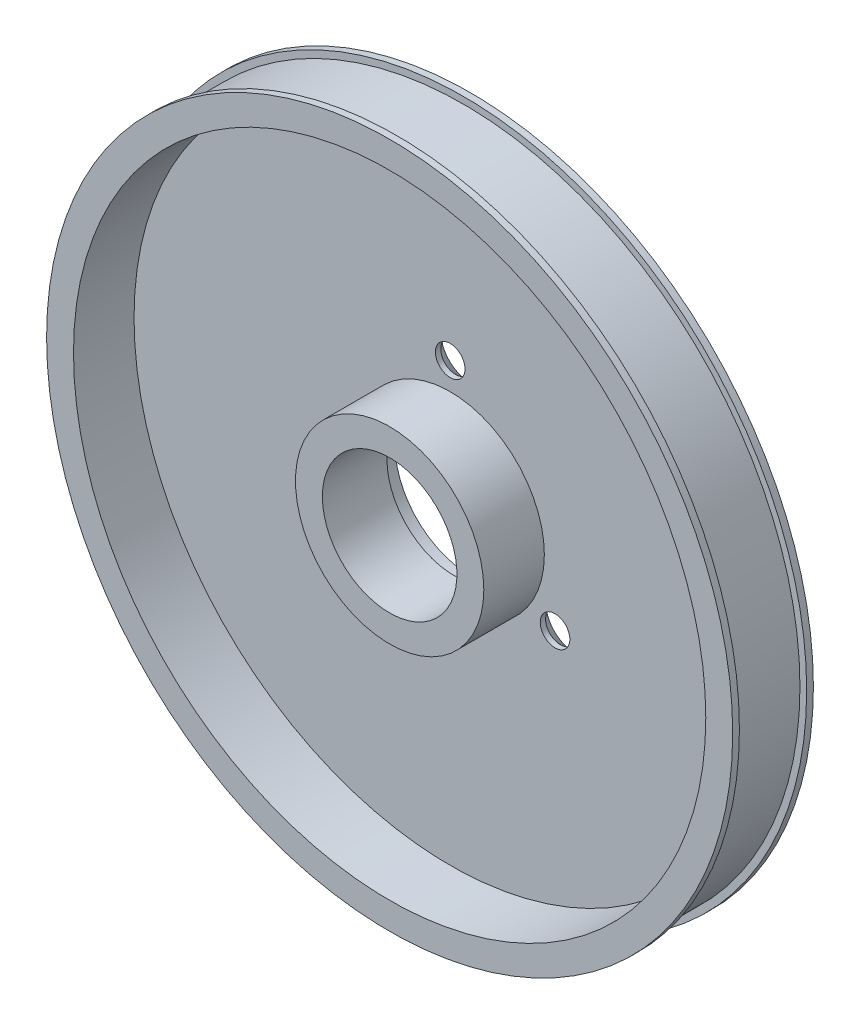
SolidWorks part; units mm, degrees
material "6061 Alloy"
ref_plane "Front Plane" through (0, 0, 0) normal (0, 0, 1) x (1, 0, 0)
ref_plane "Top Plane" through (0, 0, 0) normal (0, 1, 0) x (1, 0, 0)
ref_plane "Right Plane" through (0, 0, 0) normal (1, 0, 0) x (0, 0, -1)
sketch "Sketch1" plane through (0, 0, 0) normal (0, 1, 0) x (1, 0, 0)
  line L0 (25.5, 0) -> (0, 0)
  line L1 (0, 0) -> (0, -6)
  line L2 (0, -6) -> (25.5, -6)
  line L3 (25.5, -6) -> (25.5, -5.5)
  line L4 (25.5, -5.5) -> (25, -5.5)
  line L5 (25, -5.5) -> (25, -0.5)
  line L6 (25, -0.5) -> (25.5, -0.5)
  line L7 (25.5, -0.5) -> (25.5, 0)
  line L8 (0, 0) -> (0, -6) construction
revolve "Revolve1" add sketch "Sketch1" angle 360 about L8 reverse direction yes
hole_wizard "M42 Clearance Hole1" positions "Sketch3" profile "Sketch2" hole size "M42" standard "ANSI Metric"
sketch "Sketch3" plane through (0, 0, 6) normal (0, 0, 1) x (1, 0, 0)
  point P0 (0, 0)
sketch "Sketch2" plane through (0, 0, 6) normal (1, 0, 0) x (0, -1, 0)
  line L0 (0, 0) -> (0, 4.5)
  line L1 (0, 4.5) -> (23.5, 4.5)
  line L2 (23.5, 4.5) -> (23.5, 0)
  line L5 (23.5, 0) -> (0, 0)
  line L10 (0, 4.5) -> (-23.5, 4.5) construction
  line L11 (0, -6.35) -> (0, 107.95) construction
  dimension "Hole Dia." = 47
  dimension "Hole Depth" = 4.5
  dimension "Drill Angle" = 180
sketch "Sketch4" plane through (0, 0, 0) normal (0, 1, 0) x (1, 0, 0)
  line L0 (7, -1.5) -> (0, -1.5)
  line L1 (0, -1.5) -> (0, -6)
  line L2 (0, -6) -> (7, -6)
  line L3 (7, -6) -> (7, -1.5)
  line L4 (0, -1.5) -> (0, -6) construction
revolve "Revolve2" add sketch "Sketch4" angle 360 about L4 reverse direction yes
hole_wizard "CSK for M2 Flat Head Machine Screw1" positions "Sketch6" profile "Sketch5" countersink size "M2" standard "ANSI Metric"
sketch "Sketch6" plane through (0, 0, 0) normal (0, 0, -1) x (-1, 0, 0)
  point P0 (-7.7942, -4.5)
  point P1 (7.7942, -4.5)
  point P2 (0, 9)
sketch "Sketch5" plane through (7.7942, -4.5, 0) normal (1, 0, 0) x (0, 1, 0)
  line L0 (0, 0) -> (0, 6)
  line L1 (0, 6) -> (1.1, 6)
  line L2 (1.1, 6) -> (1.1, 1.1)
  line L3 (1.1, 1.1) -> (2.2, 0)
  line L5 (2.2, 0) -> (0, 0)
  line L6 (-1.1, 1.1) -> (-2.2, 0) construction
  line L11 (0, -6.35) -> (0, 107.95) construction
  dimension "Thru Hole Dia." = 2.2
  dimension "Thru Hole Depth" = 6
  dimension "Near C'Sink Dia." = 4.4
  dimension "Near C'Sink Angle" = 90
hole_wizard "CBORE for M8 Hex Head Bolt1" positions "Sketch8" profile "Sketch7" counterbore size "M8" standard "ANSI Metric"
sketch "Sketch8" plane through (0, 0, 0) normal (0, 0, -1) x (-1, 0, 0)
  point P0 (0, 0)
sketch "Sketch7" plane through (0, 0, 0) normal (1, 0, 0) x (0, 1, 0)
  line L0 (0, 0) -> (0, 6)
  line L1 (0, 6) -> (5, 6)
  line L3 (5, 6) -> (5, 1.2)
  line L4 (5, 1.2) -> (5.6, 1.2)
  line L5 (5.6, 1.2) -> (5.6, 0)
  line L7 (5.6, 0) -> (0, 0)
  line L11 (0, -6.35) -> (0, 107.95) construction
  dimension "Thru Hole Dia." = 10
  dimension "Thru Hole Depth" = 6
  dimension "C'Bore Dia." = 11.2
  dimension "C'Bore Depth" = 1.2
